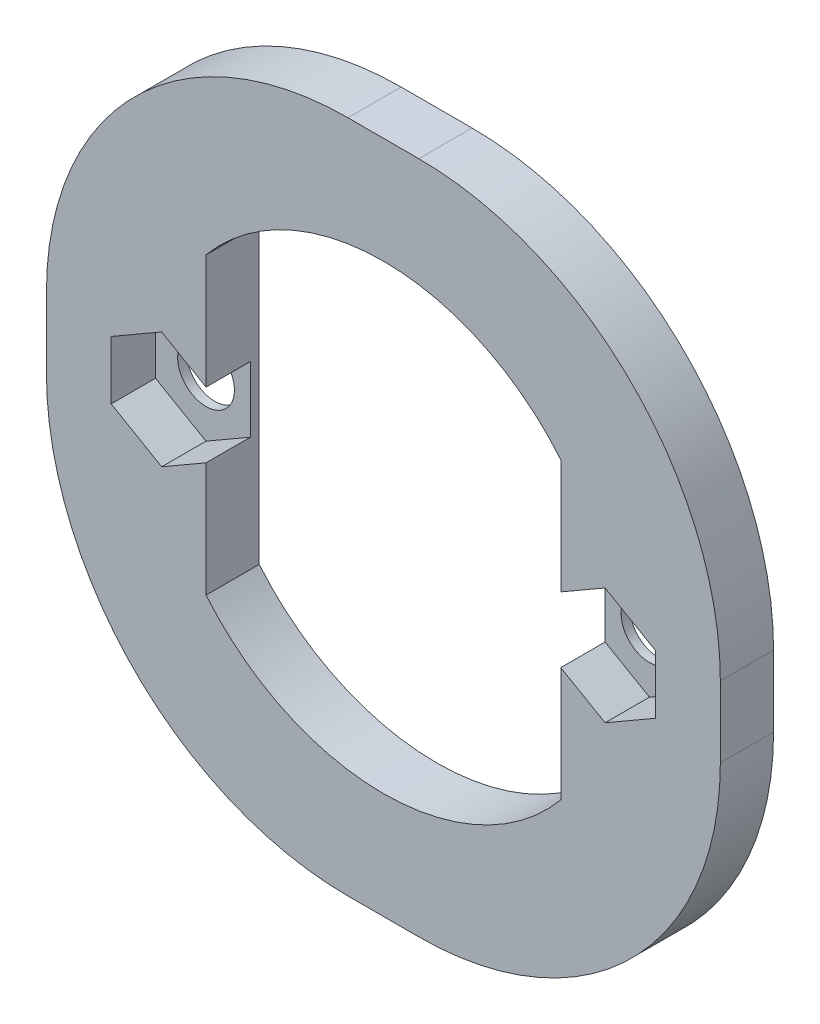
SolidWorks part; units mm, degrees
ref_plane "Płaszczyzna przednia" through (0, 0, 0) normal (0, 0, 1) x (1, 0, 0)
ref_plane "Płaszczyzna górna" through (0, 0, 0) normal (0, 1, 0) x (1, 0, 0)
ref_plane "Płaszczyzna prawa" through (0, 0, 0) normal (1, 0, 0) x (0, 0, -1)
sketch "Sketch1" plane through (0, 0, 0) normal (0, 0, 1) x (1, 0, 0)
  line L0 (0, 0) -> (11.5716, 0) construction
  line L1 (0, 0) -> (-11.5716, 0) construction
  line L2 (-9.9979, 0) -> (-8.9979, 0) construction
  line L3 (9.9979, 0) -> (8.9979, 0) construction
  line L4 (-8.9979, 0) -> (-18.9979, 0) construction
  line L5 (8.9979, 0) -> (18.9979, 0) construction
  line L6 (0, 0) -> (0, 19) construction
  line L7 (0, 0) -> (0, -19) construction
  line L8 (0, 0) -> (0, 8.0298) construction
  line L9 (-1.9979, -19) -> (1.9979, -19)
  line L10 (-18.9979, -2) -> (-18.9979, 2)
  line L11 (-1.9979, 19) -> (1.9979, 19)
  line L12 (18.9979, -2) -> (18.9979, 2)
  line L13 (-18.9979, -19) -> (18.9979, 19) construction
  line L14 (-18.9979, 19) -> (18.9979, -19) construction
  line L16 (-10, -10) -> (-9.9989, -10)
  line L17 (-10, -8.3066) -> (-10, 8.3066)
  line L18 (-10, 10) -> (-9.9989, 10)
  line L19 (10, -8.3066) -> (10, 8.3066)
  line L20 (-10, -10) -> (10, 10) construction
  line L21 (-10, 10) -> (10, -10) construction
  line L22 (9.9989, 10) -> (10, 10)
  line L23 (9.9989, -10) -> (10, -10)
  circle A0 centre (-11.5716, 0) radius 1.5737 construction
  circle A1 centre (11.5716, 0) radius 1.5737 construction
  arc A3 (-10, -8.3066) -> (10, -8.3066) centre (0, 0) ccw
  arc A4 (10, 8.3066) -> (-10, 8.3066) centre (0, 0) ccw
  arc A5 (-1.9979, -19) -> (-18.9979, -2) centre (-1.9979, -2) cw
  arc A6 (1.9979, -19) -> (18.9979, -2) centre (1.9979, -2) ccw
  arc A7 (1.9979, 19) -> (18.9979, 2) centre (1.9979, 2) cw
  arc A8 (-18.9979, 2) -> (-1.9979, 19) centre (-1.9979, 2) cw
  dimension "D1" = 1
  dimension "D5" = 17
  dimension "D2" = 1
  dimension "D3" = 20
  dimension "D4" = 20
extrude "Boss-Extrude5" add sketch "Sketch1" along normal blind 3 contours L9 L12 L11 L10 A4 L19 A3 L17 region at (-13.6387, -13.6408, 0)
sketch "Sketch2" plane through (0, 0, 3) normal (0, 0, 1) x (1, 0, 0)
  line L0 (0, 0) -> (12.5, 0) construction
  line L1 (0, 0) -> (-12.5, 0) construction
  circle A2 centre (-12.5, 0) radius 1.6
  circle A3 centre (12.5, 0) radius 1.6
extrude "Cut-Extrude2" cut sketch "Sketch2" against normal through all
sketch "Sketch3" plane through (0, 0, 3) normal (0, 0, 1) x (1, 0, 0)
  line L13 (-12.5, 3.2909) -> (-15.35, 1.6454)
  line L14 (-15.35, 1.6454) -> (-15.35, -1.6454)
  line L15 (-15.35, -1.6454) -> (-12.5, -3.2909)
  line L16 (-12.5, -3.2909) -> (-9.65, -1.6454)
  line L17 (-9.65, -1.6454) -> (-9.65, 1.6454)
  line L18 (-9.65, 1.6454) -> (-12.5, 3.2909)
  line L19 (12.5, 3.2909) -> (9.65, 1.6454)
  line L20 (9.65, 1.6454) -> (9.65, -1.6454)
  line L21 (9.65, -1.6454) -> (12.5, -3.2909)
  line L22 (12.5, -3.2909) -> (15.35, -1.6454)
  line L23 (15.35, -1.6454) -> (15.35, 1.6454)
  line L24 (15.35, 1.6454) -> (12.5, 3.2909)
  circle A0 centre (-12.5, 0) radius 2.85 construction
  circle A1 centre (12.5, 0) radius 2.85 construction
extrude "Cut-Extrude3" cut sketch "Sketch3" against normal blind 2.5
